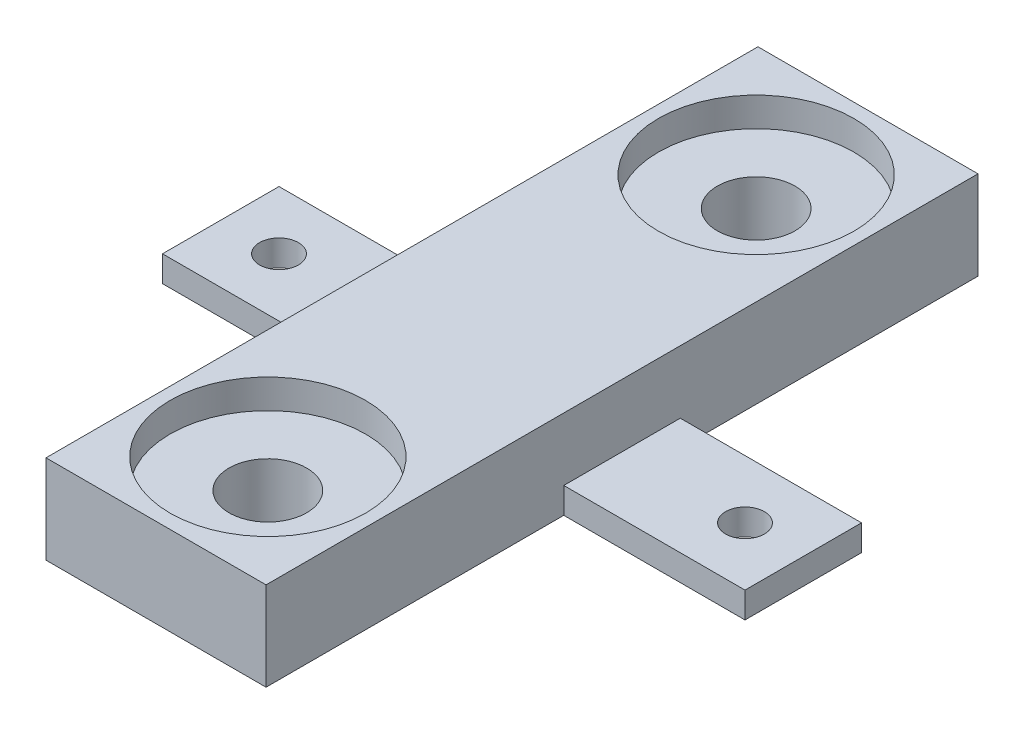
SolidWorks part; units mm, degrees
material "Nylon 101"
ref_plane "Front Plane" through (0, 0, 0) normal (0, 0, 1) x (1, 0, 0)
ref_plane "Top Plane" through (0, 0, 0) normal (0, 1, 0) x (1, 0, 0)
ref_plane "Right Plane" through (0, 0, 0) normal (1, 0, 0) x (0, 0, -1)
sketch "Sketch1" plane through (0, 0, 0) normal (0, 1, 0) x (1, 0, 0)
  line L0 (0, -18.8625) -> (0, -27.5) construction
  line L1 (-8.5, 27.5) -> (8.5, 27.5)
  line L2 (-8.5, 27.5) -> (-8.5, -27.5)
  line L3 (-8.5, -27.5) -> (8.5, -27.5)
  line L4 (8.5, 27.5) -> (8.5, -27.5)
  line L5 (-8.5, 0) -> (0, 0) construction
  line L6 (0, 18.8625) -> (0, -18.8625) construction
  line L7 (-18, 0) -> (18, 0) construction
  line L8 (-8.5, 4.5) -> (-22.5, 4.5)
  line L9 (-8.5, 4.5) -> (-8.5, -4.5)
  line L10 (-8.5, -4.5) -> (-22.5, -4.5)
  line L11 (-22.5, 4.5) -> (-22.5, -4.5)
  line L12 (8.5, 4.5) -> (22.5, 4.5)
  line L13 (8.5, 4.5) -> (8.5, -4.5)
  line L14 (8.5, -4.5) -> (22.5, -4.5)
  line L15 (22.5, 4.5) -> (22.5, -4.5)
  circle A0 centre (0, 18.8625) radius 7.55
  circle A1 centre (0, -18.8625) radius 7.55
  circle A2 centre (-18, 0) radius 1.5
  circle A3 centre (18, 0) radius 1.5
  point P24 (0, 0)
  point P26 (0, 0)
  point P28 (-22.5, 0)
  dimension "D3" = 15.1
  dimension "D7" = 3
  dimension "D1" = 55
  dimension "D2" = 17
  dimension "D4" = 37.725
  dimension "D6" = 36
  dimension "D8" = 4.5
  dimension "D9" = 9
extrude "Boss-Extrude1" add sketch "Sketch1" along normal blind 2 contours L4 L1 L2 L3 A1 A0 | L15 L12 L4 L14 A3 | L8 L11 L10 L2 A2 | A1 | A0 region at (0, 0, 0) region at (-15.3514, 0, 0) region at (15.3514, 0, 0) region at (0, 0, -18.8625) region at (0, 0, 18.8625)
extrude "Boss-Extrude2" add sketch "Sketch1<4>" along normal blind 2.6 from surface contours L4 L1 L2 L3 A1 A0 | A1 | A0 region at (0, 0, 0) region at (0, 0, -18.8625) region at (0, 0, 18.8625) starting at face at (0, 2, 0)
sketch "Sketch1<4>" plane through (0, 0, 0) normal (0, 1, 0) x (1, 0, 0) same geometry as "Sketch1"
extrude "Boss-Extrude3" add sketch "Sketch1<5>" along normal blind 2.25 from surface contours L4 L1 L2 L3 A1 A0 region at (0, 0, 0) starting at face at (0, 4.6, 0)
sketch "Sketch1<5>" plane through (0, 0, 0) normal (0, 1, 0) x (1, 0, 0) same geometry as "Sketch1"
sketch "Sketch3" plane through (0, 0, 0) normal (0, -1, 0) x (1, 0, 0)
  circle A0 centre (0, -18.8625) radius 3
  circle A1 centre (0, 18.8625) radius 3
  circle A2 centre (0, 18.8625) radius 7.55 construction
  dimension "D1" = 6
extrude "Cut-Extrude1" cut sketch "Sketch3" against normal through all
equation "\"D1@Boss-Extrude2\"= \"base_thickness\" - 2.25mm - 1.5mm"
equation "\"bottomThickness\"= .220in"
equation "\"wallThickness\"= .125in"
equation "\"wall_thickness\"= 0.125in"
equation "\"base_thickness\"= 0.25in"
